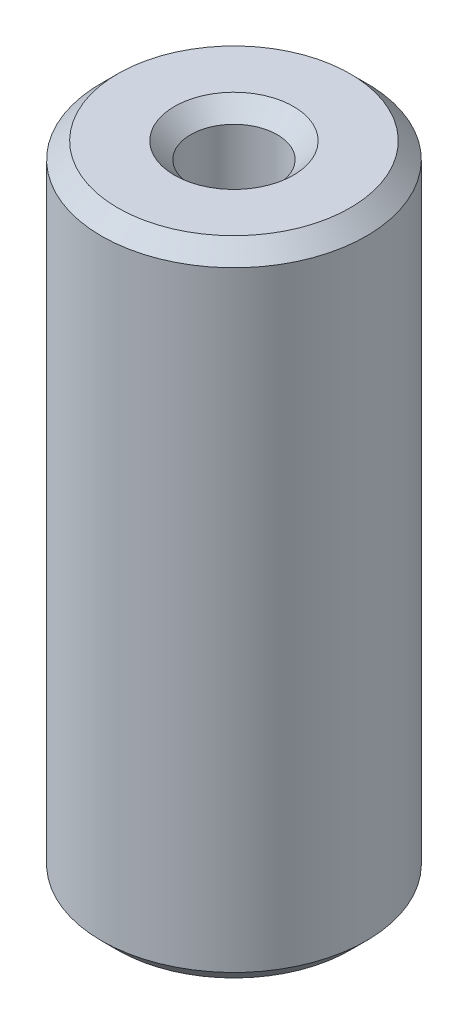
SolidWorks part; units mm, degrees
ref_plane "Front Plane" through (0, 0, 0) normal (0, 0, 1) x (1, 0, 0)
ref_plane "Top Plane" through (0, 0, 0) normal (0, 1, 0) x (1, 0, 0)
ref_plane "Right Plane" through (0, 0, 0) normal (1, 0, 0) x (0, 0, -1)
sketch "Sketch1" plane through (0, 0, 0) normal (0, 1, 0) x (1, 0, 0)
  circle A0 centre (0, 0) radius 10
  dimension "SLEEVE_OD" = 20
extrude "Boss-Extrude1" add sketch "Sketch1" along normal blind 48.5226
sketch "Sketch2" plane through (0, 0, 0) normal (0, 1, 0) x (1, 0, 0)
  circle A0 centre (0, 0) radius 3.267
  dimension "BORE_D" = 6.5341
extrude "Cut-Extrude1" cut sketch "Sketch2" along normal through all
chamfer "Chamfer1" distance 1.2284 angle 45 4 edges at (0, 48.5226, 3.267) (0, 0, 3.267) (0, 0, 10) (0, 48.5226, 10)
